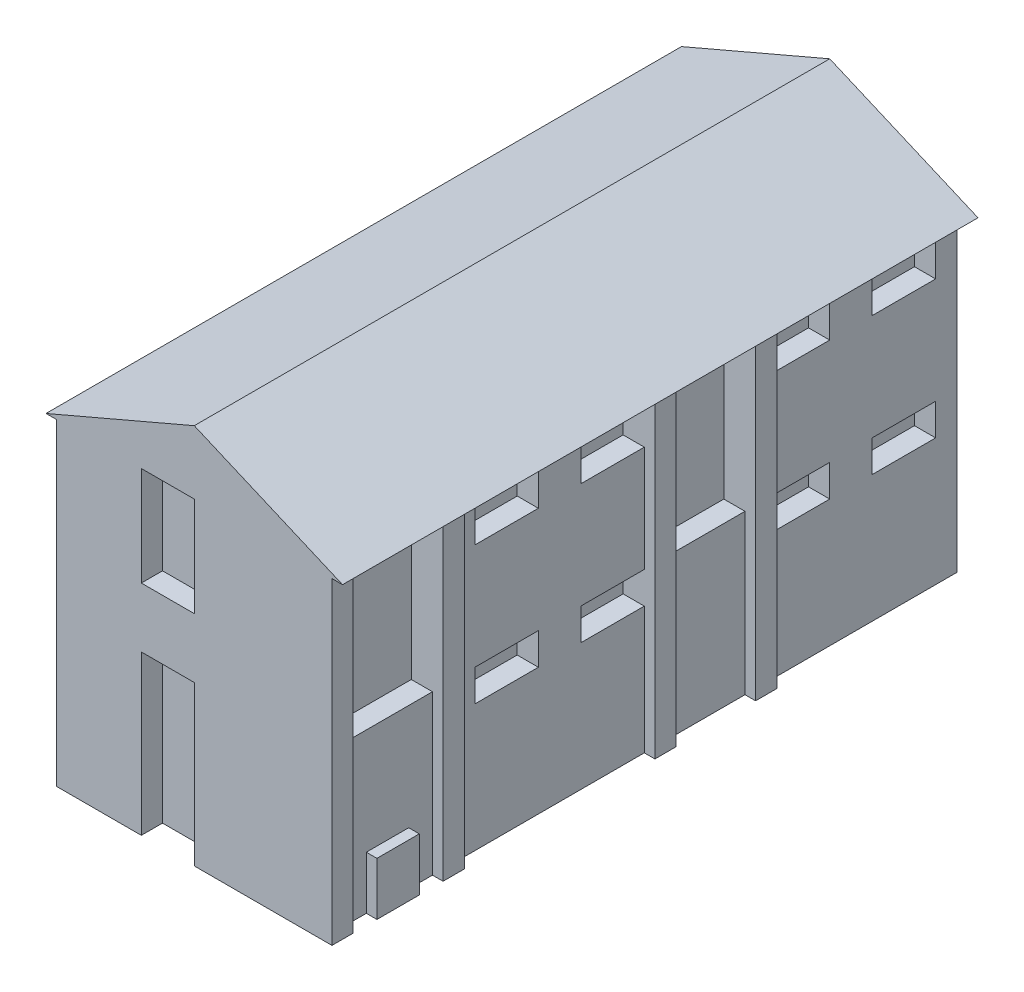
SolidWorks part; units mm, degrees
ref_plane "Alzado" through (0, 0, 0) normal (0, 0, 1) x (1, 0, 0)
ref_plane "Planta" through (0, 0, 0) normal (0, 1, 0) x (1, 0, 0)
ref_plane "Vista lateral" through (0, 0, 0) normal (1, 0, 0) x (0, 0, -1)
sketch "Croquis1" plane through (0, 0, 0) normal (0, 0, 1) x (1, 0, 0)
  line L0 (0, 7.5) -> (0, 10.5) construction
  line L1 (-6, -7.5) -> (6, -7.5)
  line L2 (-6, -7.5) -> (-6, 7.5)
  line L4 (6, -7.5) -> (6, 7.5)
  line L5 (-6, -7.5) -> (6, 7.5) construction
  line L6 (-6, 7.5) -> (6, -7.5) construction
  line L9 (-6, 7.5) -> (6, 7.5) construction
  line L10 (6, 7.5) -> (7, 7.5)
  line L11 (-6, 7.5) -> (-7, 7.5)
  line L12 (-7, 7.5) -> (0, 10.5)
  line L13 (0, 10.5) -> (7, 7.5)
  point P0 (0, 0)
  dimension "D1" = 15
  dimension "D2" = 12
  dimension "D3" = 3
  dimension "D4" = 1
  dimension "D5" = 1
extrude "Saliente-Extruir1" add sketch "Croquis1" along normal blind 30
sketch "Croquis2" plane through (6, 0, 0) normal (1, 0, 0) x (0, 0, -1)
  line L0 (-30, -7.5) -> (0, -7.5) construction
  line L1 (-30, 7.5) -> (-29, 7.5)
  line L2 (-30, 7.5) -> (-30, -7.5)
  line L3 (-30, -7.5) -> (-29, -7.5)
  line L4 (-29, 7.5) -> (-29, -7.5)
  line L5 (-30, 7.5) -> (0, 7.5) construction
  line L6 (-24.7541, 7.5) -> (-23.7541, 7.5)
  line L7 (-24.7541, 7.5) -> (-24.7541, -7.5)
  line L8 (-24.7541, -7.5) -> (-23.7541, -7.5)
  line L9 (-23.7541, 7.5) -> (-23.7541, -7.5)
  dimension "D1" = 1
  dimension "D2" = 1
extrude "Saliente-Extruir2" add sketch "Croquis2" along normal blind 0.5
sketch "Croquis3" plane through (6, 0, 0) normal (1, 0, 0) x (0, 0, -1)
  line L0 (-29, 0) -> (-14.7541, 0) construction
  line L1 (-29, -7.5) -> (-29, 7.5) construction
  line L2 (-29, 6.5) -> (-14.7541, 6.5) construction
  line L3 (0, -7.5) -> (0, 7.5) construction
  line L5 (-23.7541, -7.5) -> (-23.7541, 7.5) construction
  line L6 (-29, 6.5) -> (-24.7541, 6.5)
  line L7 (-29, 6.5) -> (-29, 0)
  line L8 (-29, 0) -> (-24.7541, 0)
  line L9 (-29, 7.5) -> (-29, -7.5)
  line L10 (-29, -7.5) -> (-24.7541, -7.5)
  line L11 (-24.7541, -7.5) -> (-24.7541, 7.5)
  line L12 (-24.7541, 7.5) -> (-29, 7.5)
  line L13 (-29, 7.5) -> (-29, -7.5) construction
  line L14 (-29, -7.5) -> (-24.7541, -7.5) construction
  line L15 (-24.7541, -7.5) -> (-24.7541, 7.5) construction
  line L17 (-24.7541, 6.5) -> (-24.7541, 0)
  line L18 (-22.7541, 6.5) -> (-19.7541, 6.5)
  line L19 (-22.7541, 6.5) -> (-22.7541, 5)
  line L20 (-22.7541, 5) -> (-19.7541, 5)
  line L21 (-19.7541, 6.5) -> (-19.7541, 5)
  line L22 (-17.7541, 6.5) -> (-17.7541, 5)
  line L23 (-17.7541, 6.5) -> (-14.7541, 6.5)
  line L24 (-14.7541, 6.5) -> (-14.7541, 5)
  line L25 (-17.7541, 5) -> (-14.7541, 5)
  line L26 (-23.7541, -7.5) -> (0, -7.5) construction
  line L28 (-14.7541, 6.5) -> (-14.7541, 0)
  line L30 (-13.7541, 6.5) -> (-13.7541, 0)
  line L32 (-10, 6.5) -> (-10, 0)
  line L34 (-9, 6.5) -> (-9, 0)
  line L35 (-1, 6.5) -> (-4, 6.5)
  line L36 (-1, 6.5) -> (-1, 5)
  line L37 (-1, 5) -> (-4, 5)
  line L38 (-4, 6.5) -> (-4, 5)
  line L40 (-14.7541, 0) -> (-14.7541, -7.5)
  line L41 (-14.7541, -7.5) -> (-13.7541, -7.5)
  line L42 (-13.7541, 0) -> (-13.7541, -7.5)
  line L43 (-13.7541, 0) -> (-10, 0) construction
  line L45 (-10, 0) -> (-10, -7.5)
  line L46 (-10, -7.5) -> (-9, -7.5)
  line L47 (-9, 0) -> (-9, -7.5)
  line L48 (-9, 0) -> (0, 0) construction
  line L49 (-6, 6.5) -> (-6, 5)
  line L50 (-6, 6.5) -> (-9, 6.5)
  line L51 (-9, 6.5) -> (-9, 5)
  line L52 (-6, 5) -> (-9, 5)
  line L53 (-22.7541, 0) -> (-22.7541, -1.5)
  line L54 (-22.7541, 0) -> (-19.7541, 0)
  line L55 (-19.7541, 0) -> (-19.7541, -1.5)
  line L56 (-22.7541, -1.5) -> (-19.7541, -1.5)
  line L57 (-17.7541, 0) -> (-17.7541, -1.5)
  line L58 (-17.7541, -1.5) -> (-14.7541, -1.5)
  line L59 (-14.7541, 0) -> (-14.7541, -1.5)
  line L60 (-17.7541, 0) -> (-14.7541, 0)
  line L61 (-6, 0) -> (-6, -1.5)
  line L62 (-6, -1.5) -> (-9, -1.5)
  line L63 (-9, 0) -> (-9, -1.5)
  line L64 (-6, 0) -> (-9, 0)
  line L65 (-1, 0) -> (-1, -1.5)
  line L66 (-1, 0) -> (-4, 0)
  line L67 (-4, 0) -> (-4, -1.5)
  line L68 (-1, -1.5) -> (-4, -1.5)
  line L69 (-27.8771, -7.5) -> (-25.8771, -7.5)
  line L71 (-27.8771, -7.5) -> (-27.8771, -5)
  line L72 (-27.8771, -5) -> (-25.8771, -5)
  line L73 (-25.8771, -7.5) -> (-25.8771, -5)
  line L74 (-26.8771, -7.5) -> (-25.8771, -5) construction
  line L75 (-27.8771, -5) -> (-26.8771, -7.5) construction
  line L77 (-13.7541, 6.5) -> (-10, 6.5)
  line L78 (-13.7541, 6.5) -> (-13.7541, 0)
  line L79 (-13.7541, 0) -> (-10, 0)
  line L80 (-10, 6.5) -> (-10, 0)
  line L82 (-14.7541, 6.5) -> (-14.7541, 7.5)
  line L83 (-14.7541, 7.5) -> (-13.7541, 7.5)
  line L84 (-13.7541, 6.5) -> (-13.7541, 7.5)
  line L88 (-10, 6.5) -> (-10, 7.5)
  line L89 (-10, 7.5) -> (-9, 7.5)
  line L90 (-9, 6.5) -> (-9, 7.5)
  line L92 (-13.7541, 6.5) -> (-10, 6.5) construction
  line L93 (-9, 6.5) -> (0, 6.5) construction
  line L98 (-24.7541, 7.5) -> (-29, 7.5)
  point P44 (-26.8771, -7.5)
  line M39 (-29, 7.5) -> (-29, -7.5)
  line M40 (-29, -7.5) -> (-24.7541, -7.5)
  line M41 (-24.7541, -7.5) -> (-24.7541, 7.5)
  dimension "D3" = 3
  dimension "D4" = 1.5
  dimension "D5" = 1
  dimension "D7" = 1
  dimension "D8" = 3
  dimension "D10" = 2
  dimension "D11" = 2
  dimension "D12" = 1
  dimension "D13" = 1
  dimension "D15" = 2
  dimension "D2" = 0
  dimension "D6" = 2
  dimension "D9" = 2
  dimension "D14" = 2
extrude "Saliente-Extruir3" add sketch "Croquis3" along normal blind 0.5 contours L42 L30 L24 L28 L40 L41 | L47 L34 L32 L45 L46 region at (6, 0, 14.2541) region at (6, 0, 9.5)
extrude "Cortar-Extruir1" cut sketch "Croquis3<3>" against normal blind 1 contours L21 L18 L19 L20 | L22 L25 L24 L23 | L60 L57 L58 L40 | L53 L56 L55 L54 | L61 L64 L47 L62 | L68 L65 L66 L67 | L30 L79 L32 L77 | L52 L49 L50 L34 | L35 L38 L37 L36 | L8 L6 M39 M41 region at (6, 3.25, 26.8771) region at (6, 5.75, 21.2541) region at (6, 5.75, 16.2541) region at (6, -0.75, 16.2541) region at (6, 3.25, 11.8771) region at (6, 5.75, 7.5) region at (6, -0.75, 7.5) region at (6, 5.75, 2.5) region at (6, -0.75, 21.2541) region at (6, -0.75, 2.5)
sketch "Croquis3<3>" plane through (6, 0, 0) normal (1, 0, 0) x (0, 0, -1) same geometry as "Croquis3"
extrude "Saliente-Extruir4" add sketch "Croquis3<4>" along normal blind 0.5 contours L73 L72 L71 M40 region at (6, -6.25, 26.8771)
sketch "Croquis3<4>" plane through (6, 0, 0) normal (1, 0, 0) x (0, 0, -1) same geometry as "Croquis3"
sketch "Croquis7" plane through (-6, 0, 0) normal (-1, 0, 0) x (0, 0, 1)
  line L0 (30, 7.5) -> (0, 7.5) construction
  line L1 (30, -7.5) -> (29, -7.5)
  line L2 (30, -7.5) -> (30, 7.5)
  line L3 (30, 7.5) -> (29, 7.5)
  line L4 (29, -7.5) -> (29, 7.5)
  dimension "D1" = 1
extrude "Saliente-Extruir5" add sketch "Croquis7" along normal blind 0.5
sketch "Croquis8" plane through (0, 0, 30) normal (0, 0, 1) x (1, 0, 0)
  line L0 (0, -7.5) -> (0, 10.5) construction
  line L2 (0, -7.5) -> (-2.5, -7.5)
  line L3 (0, -7.5) -> (0, 0)
  line L4 (0, 0) -> (-2.5, 0)
  line L5 (-2.5, -7.5) -> (-2.5, 0)
  line L6 (0, 7.5) -> (-2.5, 7.5)
  line L7 (6.5, -7.5) -> (6.5, 7.5)
  line L8 (6.5, 7.5) -> (7, 7.5)
  line L9 (7, 7.5) -> (0, 10.5)
  line L10 (0, 10.5) -> (-7, 7.5)
  line L11 (-7, 7.5) -> (-6.5, 7.5)
  line L12 (-6.5, 7.5) -> (-6.5, -7.5)
  line L13 (-6.5, -7.5) -> (6.5, -7.5)
  line L14 (6.5, -7.5) -> (6.5, 7.5)
  line L15 (6.5, 7.5) -> (7, 7.5)
  line L16 (7, 7.5) -> (0, 10.5)
  line L17 (0, 10.5) -> (-7, 7.5)
  line L18 (-7, 7.5) -> (-6.5, 7.5)
  line L19 (-6.5, 7.5) -> (-6.5, -7.5)
  line L20 (-6.5, -7.5) -> (6.5, -7.5)
  line L21 (0, 7.5) -> (0, 2.8159)
  line L22 (0, 2.8159) -> (-2.5, 2.8159)
  line L23 (-2.5, 7.5) -> (-2.5, 2.8159)
  dimension "D2" = 2.5
  dimension "D3" = 2.5
  dimension "D1" = 0
extrude "Cortar-Extruir2" cut sketch "Croquis8" against normal blind 1 contours L21 L6 L23 L22 | L3 L2 L5 L4
sketch "Croquis10" plane through (-6, 0, 0) normal (-1, 0, 0) x (0, 0, 1)
  line L1 (0, 7.5) -> (1, 7.5)
  line L2 (0, 7.5) -> (0, -7.5)
  line L3 (0, -7.5) -> (1, -7.5)
  line L4 (29, -7.5) -> (29, 7.5)
  line L5 (29, 7.5) -> (0, 7.5)
  line L6 (0, 7.5) -> (0, -7.5)
  line L7 (0, -7.5) -> (29, -7.5)
  line L8 (29, -7.5) -> (29, 7.5) construction
  line L9 (29, 7.5) -> (0, 7.5) construction
  line L10 (0, 7.5) -> (0, -7.5) construction
  line L11 (0, -7.5) -> (29, -7.5) construction
  line L12 (1, 7.5) -> (1, -7.5)
  line L13 (14.5, 7.5) -> (12.5, 7.5)
  line L14 (14.5, 7.5) -> (14.5, -7.5)
  line L15 (14.5, -7.5) -> (12.5, -7.5)
  line L16 (12.5, 7.5) -> (12.5, -7.5)
  dimension "D2" = 1
  dimension "D3" = 2
  dimension "D1" = 0
extrude "Saliente-Extruir6" add sketch "Croquis10" along normal blind 0.5
sketch "Croquis11" plane through (-6, 0, 0) normal (-1, 0, 0) x (0, 0, 1)
  line L0 (12.5, 0) -> (1, 0) construction
  line L1 (6.75, 7.5) -> (6.75, 6.5) construction
  line L2 (6.75, 7.5) -> (6.75, -7.5) construction
  line L3 (12.5, 6.5) -> (1, 6.5) construction
  line L4 (1, 7.5) -> (1, -7.5)
  line L5 (1, -7.5) -> (12.5, -7.5)
  line L6 (12.5, -7.5) -> (12.5, 7.5)
  line L7 (12.5, 7.5) -> (1, 7.5)
  line L8 (1, 7.5) -> (1, -7.5) construction
  line L9 (1, -7.5) -> (12.5, -7.5) construction
  line L10 (12.5, -7.5) -> (12.5, 7.5) construction
  line L11 (12.5, 7.5) -> (1, 7.5) construction
  line L12 (6.75, -1) -> (6.75, 1) construction
  line L13 (1, 1) -> (12.5, 1) construction
  line L14 (12.5, 1) -> (12.5, -1) construction
  line L15 (12.5, -1) -> (1, -1) construction
  line L16 (5.5, 6.5) -> (5.5, 1)
  line L17 (1, 6.5) -> (3.5, 6.5)
  line L18 (1, 6.5) -> (1, 1)
  line L19 (1, 1) -> (3.5, 1)
  line L20 (3.5, 6.5) -> (3.5, 1)
  line L21 (5.5, 6.5) -> (8, 6.5)
  line L22 (8, 6.5) -> (8, 1)
  line L23 (5.5, 1) -> (8, 1)
  line L24 (10, 6.5) -> (10, 1)
  line L25 (10, 6.5) -> (12.5, 6.5)
  line L26 (12.5, 6.5) -> (12.5, 1)
  line L27 (10, 1) -> (12.5, 1)
  line L28 (5.5, -1) -> (5.5, -6.5)
  line L29 (5.5, -1) -> (8, -1)
  line L30 (8, -1) -> (8, -6.5)
  line L31 (5.5, -6.5) -> (8, -6.5)
  line L32 (10, -1) -> (10, -6.5)
  line L33 (10, -1) -> (12.5, -1)
  line L34 (12.5, -1) -> (12.5, -6.5)
  line L35 (10, -6.5) -> (12.5, -6.5)
  line L36 (1, -1) -> (1, -6.5)
  line L37 (1, -1) -> (3.5, -1)
  line L38 (3.5, -1) -> (3.5, -6.5)
  line L39 (1, -6.5) -> (3.5, -6.5)
  point P14 (6.75, 0)
  dimension "D2" = 1
  dimension "D3" = 2
  dimension "D4" = 2.5
  dimension "D1" = 0
  dimension "D5" = 3
  dimension "D6" = 2
extrude "Cortar-Extruir3" cut sketch "Croquis11" against normal blind 1
sketch "Croquis12" plane through (-6, 0, 0) normal (-1, 0, 0) x (0, 0, 1)
  line L0 (12.5, 6.5) -> (10, 6.5) construction
  line L1 (14.5, -7.5) -> (18, -7.5)
  line L2 (14.5, -7.5) -> (14.5, -1)
  line L3 (14.5, -1) -> (18, -1)
  line L4 (14.5, 7.5) -> (14.5, -7.5)
  line L5 (14.5, -7.5) -> (29, -7.5)
  line L6 (29, -7.5) -> (29, 7.5)
  line L7 (29, 7.5) -> (14.5, 7.5)
  line L8 (14.5, 7.5) -> (14.5, -7.5) construction
  line L9 (14.5, -7.5) -> (29, -7.5) construction
  line L10 (29, -7.5) -> (29, 7.5) construction
  line L11 (29, 7.5) -> (14.5, 7.5) construction
  line L12 (18, -7.5) -> (18, -1)
  line L13 (14.5, 6.5) -> (18, 6.5)
  line L14 (14.5, 6.5) -> (14.5, 4.5)
  line L15 (14.5, 4.5) -> (18, 4.5)
  line L16 (18, 6.5) -> (18, 4.5)
  line L17 (20, 6.5) -> (22.5, 6.5)
  line L18 (20, 6.5) -> (20, 1)
  line L19 (20, 1) -> (22.5, 1)
  line L20 (22.5, 6.5) -> (22.5, 1)
  line L21 (24.5, 6.5) -> (27, 6.5)
  line L22 (24.5, 6.5) -> (24.5, 1)
  line L23 (24.5, 1) -> (27, 1)
  line L24 (27, 6.5) -> (27, 1)
  line L26 (10, 1) -> (12.5, 1) construction
  line L30 (20, -1) -> (20, -6.5)
  line L31 (20, -1) -> (22.5, -1)
  line L32 (22.5, -1) -> (22.5, -6.5)
  line L33 (20, -6.5) -> (22.5, -6.5)
  line L34 (24.5, -1) -> (24.5, -6.5)
  line L35 (24.5, -1) -> (27, -1)
  line L36 (27, -1) -> (27, -6.5)
  line L37 (24.5, -6.5) -> (27, -6.5)
  dimension "D2" = 3.5
  dimension "D3" = 3.5
  dimension "D4" = 6.5
  dimension "D5" = 2
  dimension "D6" = 5.5
  dimension "D7" = 0
  dimension "D8" = 0
  dimension "D9" = 0
  dimension "D10" = 0
  dimension "D11" = 5.5
  dimension "D12" = 2
  dimension "D13" = 2
  dimension "D14" = 2.5
  dimension "D15" = 2.5
  dimension "D16" = 2
  dimension "D1" = 0
extrude "Cortar-Extruir4" cut sketch "Croquis12" against normal blind 1
sketch "Croquis13" plane through (0, -7.5, 0) normal (0, -1, 0) x (1, 0, 0)
  line L0 (-6.5, 30) -> (6, 0) construction
  line L1 (6.5, 30) -> (6, 28.8462) construction
  line L2 (-0.1275, 14.7059) -> (-6.5, 0) construction
  line L36 (-5, 18) -> (-5, 14.5)
  line L37 (-5, 14.5) -> (-6.5, 14.5)
  line L38 (-6.5, 14.5) -> (-6.5, 12.5)
  line L39 (-6.5, 12.5) -> (-6, 12.5)
  line L40 (-6, 12.5) -> (-6, 1)
  line L41 (-6, 1) -> (-6.5, 1)
  line L42 (-6.5, 1) -> (-6.5, 0)
  line L43 (-6.5, 0) -> (6, 0)
  line L44 (6, 0) -> (6, 9)
  line L45 (6, 9) -> (6.5, 9)
  line L46 (6.5, 9) -> (6.5, 10)
  line L47 (6.5, 10) -> (6, 10)
  line L48 (6, 10) -> (6, 13.7541)
  line L49 (6, 13.7541) -> (6.5, 13.7541)
  line L50 (6.5, 13.7541) -> (6.5, 14.7541)
  line L51 (6.5, 14.7541) -> (6, 14.7541)
  line L52 (6, 14.7541) -> (6, 23.7541)
  line L53 (6, 23.7541) -> (6.5, 23.7541)
  line L54 (6.5, 23.7541) -> (6.5, 24.7541)
  line L55 (6.5, 24.7541) -> (6, 24.7541)
  line L56 (6, 24.7541) -> (6, 25.8771)
  line L57 (6, 25.8771) -> (6.5, 25.8771)
  line L58 (6.5, 25.8771) -> (6.5, 27.8771)
  line L59 (6.5, 27.8771) -> (6, 27.8771)
  line L60 (6, 27.8771) -> (6, 29)
  line L61 (6, 29) -> (6.5, 29)
  line L62 (6.5, 29) -> (6.5, 30)
  line L63 (6.5, 30) -> (0, 30)
  line L64 (0, 30) -> (0, 29)
  line L65 (0, 29) -> (-2.5, 29)
  line L66 (-2.5, 29) -> (-2.5, 30)
  line L67 (-2.5, 30) -> (-6.5, 30)
  line L68 (-6.5, 30) -> (-6.5, 29)
  line L69 (-6.5, 29) -> (-6, 29)
  line L70 (-6, 29) -> (-6, 18)
  line L71 (-6, 18) -> (-5, 18)
  line L72 (-5, 18) -> (-5, 14.5) construction
  line L73 (-5, 14.5) -> (-6.5, 14.5) construction
  line L74 (-6.5, 14.5) -> (-6.5, 12.5) construction
  line L75 (-6.5, 12.5) -> (-6, 12.5) construction
  line L76 (-6, 12.5) -> (-6, 1) construction
  line L77 (-6, 1) -> (-6.5, 1) construction
  line L78 (-6.5, 1) -> (-6.5, 0) construction
  line L79 (-6.5, 0) -> (6, 0) construction
  line L80 (6, 0) -> (6, 9) construction
  line L81 (6, 9) -> (6.5, 9) construction
  line L82 (6.5, 9) -> (6.5, 10) construction
  line L83 (6.5, 10) -> (6, 10) construction
  line L84 (6, 10) -> (6, 13.7541) construction
  line L85 (6, 13.7541) -> (6.5, 13.7541) construction
  line L86 (6.5, 13.7541) -> (6.5, 14.7541) construction
  line L87 (6.5, 14.7541) -> (6, 14.7541) construction
  line L88 (6, 14.7541) -> (6, 23.7541) construction
  line L89 (6, 23.7541) -> (6.5, 23.7541) construction
  line L90 (6.5, 23.7541) -> (6.5, 24.7541) construction
  line L91 (6.5, 24.7541) -> (6, 24.7541) construction
  line L92 (6, 24.7541) -> (6, 25.8771) construction
  line L93 (6, 25.8771) -> (6.5, 25.8771) construction
  line L94 (6.5, 25.8771) -> (6.5, 27.8771) construction
  line L95 (6.5, 27.8771) -> (6, 27.8771) construction
  line L96 (6, 27.8771) -> (6, 29) construction
  line L97 (6, 29) -> (6.5, 29) construction
  line L98 (6.5, 29) -> (6.5, 30) construction
  line L99 (6.5, 30) -> (0, 30) construction
  line L100 (0, 30) -> (0, 29) construction
  line L101 (0, 29) -> (-2.5, 29) construction
  line L102 (-2.5, 29) -> (-2.5, 30) construction
  line L103 (-2.5, 30) -> (-6.5, 30) construction
  line L104 (-6.5, 30) -> (-6.5, 29) construction
  line L105 (-6.5, 29) -> (-6, 29) construction
  line L106 (-6, 29) -> (-6, 18) construction
  line L107 (-6, 18) -> (-5, 18) construction
  circle A0 centre (-0.1275, 14.7059) radius 1.575
  dimension "D2" = 3.15
  dimension "D1" = 0
extrude "Cortar-Extruir5" cut sketch "Croquis13" against normal blind 2.5
